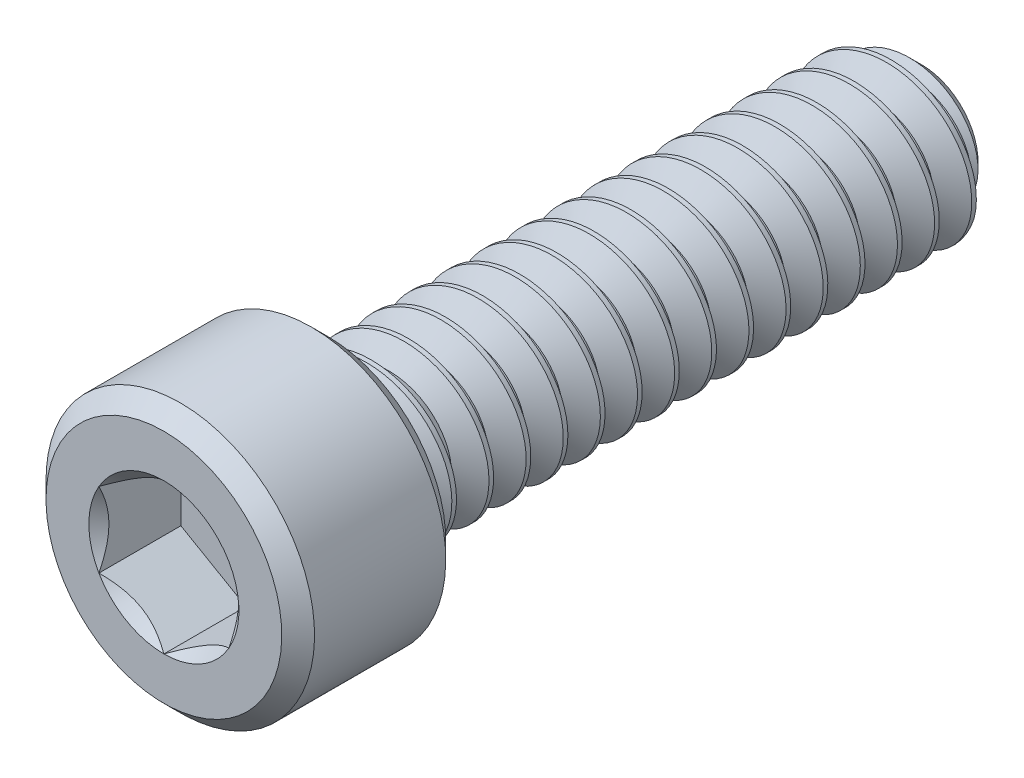
SolidWorks part; units mm, degrees
ref_plane "Front Plane" through (0, 0, 0) normal (0, 0, 1) x (1, 0, 0)
ref_plane "Top Plane" through (0, 0, 0) normal (0, 1, 0) x (1, 0, 0)
ref_plane "Right Plane" through (0, 0, 0) normal (1, 0, 0) x (0, 0, -1)
sketch "Sketch1" plane through (0, 0, 0) normal (1, 0, 0) x (0, 0, -1)
  line L0 (8.1026, 0) -> (-8.1026, 0) construction
  line L1 (-8.1026, 0) -> (-8.1026, 2.5197)
  line L2 (-8.1026, 2.5197) -> (-7.7521, 2.8702)
  line L3 (-7.7521, 2.8702) -> (-4.9479, 2.8702)
  line L4 (-4.9479, 2.8702) -> (-4.5974, 2.5197)
  line L5 (-4.5974, 2.5197) -> (-4.5974, 1.7526)
  line L6 (-4.5974, 1.7526) -> (7.547, 1.7526)
  line L7 (7.547, 1.7526) -> (8.1026, 1.197)
  line L8 (8.1026, 1.197) -> (8.1026, 0)
  line L9 (8.053, 1.8385) -> (8.8467, 1.8385) construction
  line L10 (8.8467, 1.8385) -> (8.4499, 1.1511) construction
  line L11 (8.4499, 1.1511) -> (8.053, 1.8385) construction
  line L12 (8.1026, 1.7526) -> (8.7971, 1.7526) construction
  line L13 (8.4499, 1.8385) -> (8.4499, 1.7526) construction
  line L14 (8.4003, 1.237) -> (8.4995, 1.237) construction
  line L15 (8.4499, 1.237) -> (8.4499, 1.1511) construction
  line L16 (8.0778, 1.7956) -> (8.8219, 1.7956)
  line L17 (8.8219, 1.7956) -> (8.4995, 1.237)
  line L18 (8.4995, 1.237) -> (8.4003, 1.237)
  line L19 (8.4003, 1.237) -> (8.0778, 1.7956)
  line L20 (7.547, -1.7526) -> (6.1182, -1.7526) construction
  point P4 (0, 0)
  point P25 (8.4499, 1.7956)
  point P26 (8.1026, 1.7526)
  point P33 (6.1182, -1.7526)
  dimension "Head Ht" = 3.5052
  dimension "Screw Size" = 3.5052
  dimension "Head Dia" = 5.7404
  dimension "D1" = 45
  dimension "D2" = 45
  dimension "D3" = 0.3505
  dimension "D4" = 0.3505
  dimension "Pitch" = 0.7937
  dimension "D5" = 0.0992
  dimension "D6" = 0.5556
  dimension "D7" = 1.4287
  dimension "Length" = 12.7
sketch "Sketch2" plane through (0, 0, 0) normal (0, 0, 1) x (1, 0, 0)
  line L1 (0, 1.604) -> (-1.3891, 0.802)
  line L2 (-1.3891, 0.802) -> (-1.3891, -0.802)
  line L3 (-1.3891, -0.802) -> (0, -1.604)
  line L4 (0, -1.604) -> (1.3891, -0.802)
  line L5 (1.3891, -0.802) -> (1.3891, 0.802)
  line L6 (1.3891, 0.802) -> (0, 1.604)
  circle A0 centre (0, 0) radius 1.3891 construction
  circle A1 centre (0, 0) radius 2.8702
  point P1 (0, 2.8702)
  dimension "D1" = 5.7404
  dimension "Drive Size" = 2.7781
sketch "Sketch3" plane through (0, 0, 0) normal (1, 0, 0) x (0, 0, -1)
  line L0 (8.1026, 0) -> (-8.1026, 0) construction
  line L1 (-8.1026, 0) -> (-8.1026, 2.5197) construction
  line L2 (-8.1026, 2.5197) -> (-7.7521, 2.8702) construction
  line L3 (-7.7521, 2.8702) -> (-4.9479, 2.8702) construction
  line L4 (-4.9479, 2.8702) -> (-4.5974, 2.5197) construction
  line L5 (-4.5974, 2.5197) -> (-4.5974, 1.7526) construction
  line L6 (-4.5974, 1.7526) -> (7.547, 1.7526) construction
  line L7 (7.547, 1.7526) -> (8.1026, 1.197) construction
  line L8 (8.1026, 1.197) -> (8.1026, 0) construction
  line L9 (8.1026, 0) -> (-8.1026, 0)
  line L10 (-8.1026, 0) -> (-8.1026, 2.5197)
  line L11 (-8.1026, 2.5197) -> (-7.7521, 2.8702)
  line L12 (-7.7521, 2.8702) -> (-4.9479, 2.8702)
  line L13 (-4.9479, 2.8702) -> (-4.5974, 2.5197)
  line L14 (-4.5974, 2.5197) -> (-4.5974, 1.7526)
  line L15 (-4.5974, 1.7526) -> (7.547, 1.7526)
  line L16 (7.547, 1.7526) -> (8.1026, 1.197)
  line L17 (8.1026, 1.197) -> (8.1026, 0)
revolve "Revolve1" add sketch "Sketch3" angle 360 about L0
sketch "Sketch4" plane through (0, 0, 8.1026) normal (0, 0, 1) x (1, 0, 0)
  line L0 (0, -1.604) -> (1.3891, -0.802) construction
  line L1 (1.3891, -0.802) -> (1.3891, 0.802) construction
  line L2 (1.3891, 0.802) -> (0, 1.604) construction
  line L3 (0, 1.604) -> (-1.3891, 0.802) construction
  line L4 (-1.3891, 0.802) -> (-1.3891, -0.802) construction
  line L5 (-1.3891, -0.802) -> (0, -1.604) construction
  line L6 (0, -1.604) -> (1.3891, -0.802)
  line L7 (1.3891, -0.802) -> (1.3891, 0.802)
  line L8 (1.3891, 0.802) -> (0, 1.604)
  line L9 (0, 1.604) -> (-1.3891, 0.802)
  line L10 (-1.3891, 0.802) -> (-1.3891, -0.802)
  line L11 (-1.3891, -0.802) -> (0, -1.604)
extrude "Cut-Extrude1" cut sketch "Sketch4" against normal blind 1.7526
sketch "Sketch5" plane through (0, 0, 8.1026) normal (0, 0, 1) x (1, 0, 0)
  circle A0 centre (0, 0) radius 1.604
extrude "Cut-Extrude3" cut sketch "Sketch5" against normal through all draft 45
split "Split1" bodies to split 107 resulting bodies 108 109 split by face at (0, 2.5197, 4.5974)
sketch "Sketch6" plane through (0, 0, -8.1026) normal (0, 0, -1) x (-1, 0, 0)
  circle A0 centre (0, 0) radius 1.7526 construction
  circle A1 centre (0, 0) radius 1.7526
curve "Helix/Spiral1" pitch 0.7937 height 13.4937 radius 1.7526 centre (0, 0, -8.1026) axis (0, 0, 1) start towards (0, 1, 0)
sketch "Sketch7" plane through (0, 0, 0) normal (1, 0, 0) x (0, 0, -1)
  line L0 (8.0778, 1.7956) -> (8.8219, 1.7956) construction
  line L1 (8.8219, 1.7956) -> (8.4995, 1.237) construction
  line L2 (8.4995, 1.237) -> (8.4003, 1.237) construction
  line L3 (8.4003, 1.237) -> (8.0778, 1.7956) construction
  line L4 (8.0778, 1.7956) -> (8.8219, 1.7956)
  line L5 (8.8219, 1.7956) -> (8.4995, 1.237)
  line L6 (8.4995, 1.237) -> (8.4003, 1.237)
  line L7 (8.4003, 1.237) -> (8.0778, 1.7956)
sweep "Cut-Sweep1" cut profiles "Sketch7" path "Helix/Spiral1" align with end faces yes
sketch "Sketch8" plane through (0, 0, 4.5974) normal (0, 0, -1) x (-1, 0, 0)
  circle A1 centre (0, 0) radius 1.7526
extrude "Boss-Extrude1" add sketch "Sketch8" along normal up to next (12.7 mm away) draft 20
equation "\"D3@Sketch1\"=\"Head Ht@Sketch1\"/10"
equation "\"D4@Sketch1\"=\"Head Ht@Sketch1\"/10"
equation "\"D5@Sketch1\"=\"Pitch@Sketch1\"/8"
equation "\"D6@Sketch1\"=\"Pitch@Sketch1\"*.7"
equation "\"D7@Sketch1\"=\"Pitch@Sketch1\"*2.5-\"D6@Sketch1\""
equation "\"D1@Cut-Extrude1\"=\"Head Ht@Sketch1\"/2"
equation "\"D4@Helix/Spiral1\"=\"Pitch@Sketch1\""
equation "\"D3@Helix/Spiral1\"=\"Length@Sketch1\"+\"D4@Helix/Spiral1\""
